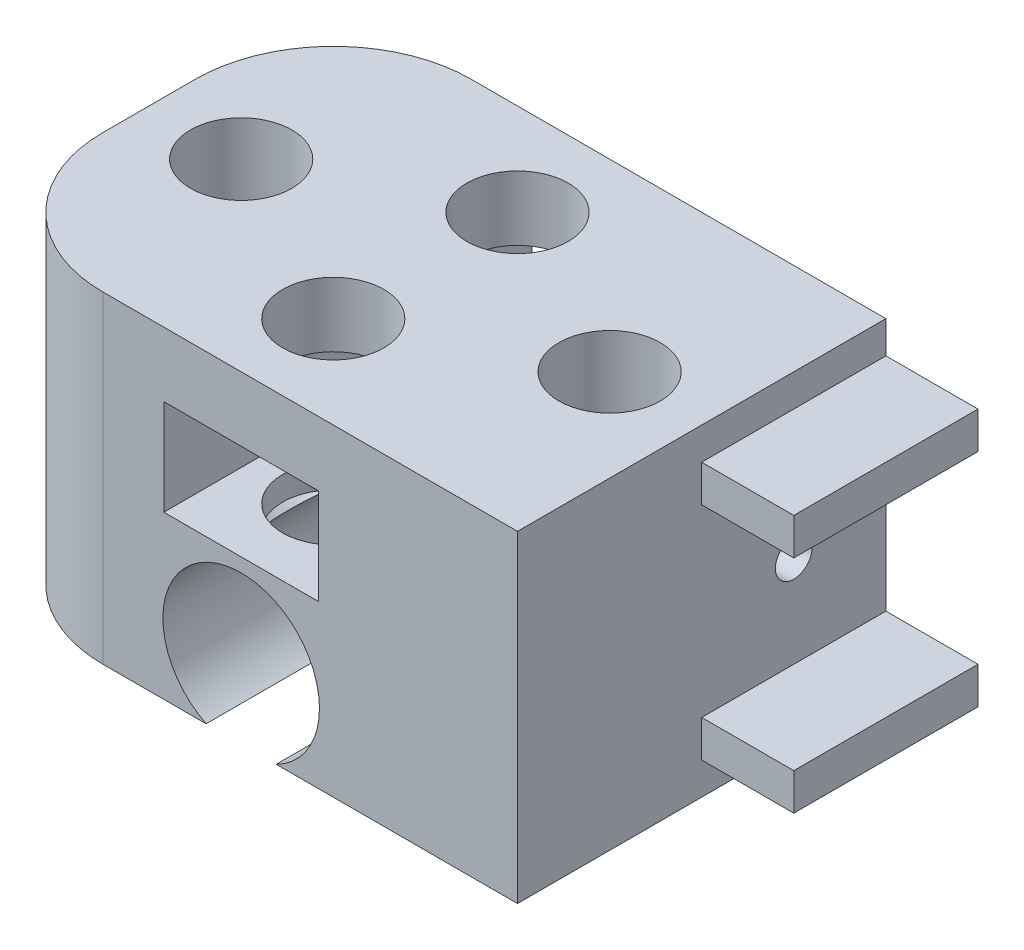
SolidWorks part; units mm, degrees
material "ABS PC"
ref_plane "Front Plane" through (0, 0, 0) normal (0, 0, 1) x (1, 0, 0)
ref_plane "Top Plane" through (0, 0, 0) normal (0, 1, 0) x (1, 0, 0)
ref_plane "Right Plane" through (0, 0, 0) normal (1, 0, 0) x (0, 0, -1)
sketch "Sketch1" plane through (0, 0, 0) normal (0, 0, 1) x (1, 0, 0)
  line L0 (0, 0) -> (30, 0)
  line L1 (0, 0) -> (0, 17.5)
  line L2 (30, 0) -> (30, 17.5)
  line L3 (0, 17.5) -> (30, 17.5)
  dimension "D1" = 30
  dimension "D2" = 17.5
extrude "Boss-Extrude1" add sketch "Sketch1" along normal blind 20
sketch "Sketch2" plane through (0, 0, 20) normal (0, 0, 1) x (1, 0, 0)
  line L0 (10.8, 8.8) -> (19.2, 8.8)
  line L1 (10.8, 8.8) -> (10.8, 14)
  line L2 (19.2, 8.8) -> (19.2, 14)
  line L3 (10.8, 14) -> (19.2, 14)
  line L5 (0, 17.5) -> (0, 0) construction
  line L6 (30, 17.5) -> (0, 17.5) construction
  circle A0 centre (15, 3.8) radius 4.25
  dimension "D1" = 8.5
  dimension "D7" = 15
  dimension "D2" = 8.4
  dimension "D3" = 5.2
  dimension "D4" = 4.2
  dimension "D5" = 5
  dimension "D6" = 3.5
extrude "Cut-Extrude1" cut sketch "Sketch2" against normal through all
hole_wizard "Ø5.5 (5.5) Diameter Hole1" positions "Sketch5" profile "Sketch4" hole size "Ø5.5" standard "Ansi Metric"
sketch "Sketch5" plane through (0, 17.5, 0) normal (0, 1, 0) x (-1, 0, 0)
  line L1 (-30, 20) -> (0, 20) construction
  line L2 (-30, 0) -> (0, 0) construction
  line L3 (0, 20) -> (0, 0) construction
  point P1 (-15, 15)
  point P12 (-15, 5)
  dimension "D1" = 5
  dimension "D2" = 5
  dimension "D3" = 15
sketch "Sketch4" plane through (15, 17.5, 15) normal (1, 0, 0) x (0, 0, 1)
  line L0 (0, 0) -> (0, 11.6524)
  line L1 (0, 11.6524) -> (2.75, 10)
  line L2 (2.75, 10) -> (2.75, 0)
  line L5 (2.75, 0) -> (0, 0)
  line L10 (0, 11.6524) -> (-2.75, 10) construction
  line L11 (0, -6.35) -> (0, 107.95) construction
  dimension "Hole Dia." = 5.5
  dimension "Hole Depth" = 10
  dimension "Drill Angle" = 118
hole_wizard "Ø5.5 (5.5) Diameter Hole2" positions "Sketch11" profile "Sketch10" hole size "Ø5.5" standard "Ansi Metric" end condition through all
sketch "Sketch11" plane through (0, 17.5, 0) normal (0, 1, 0) x (-1, 0, 0)
  line L0 (-30, 0) -> (0, 0) construction
  line L1 (-30, 20) -> (-30, 0) construction
  line L2 (0, 20) -> (0, 0) construction
  point P0 (-25, 10)
  point P1 (-5, 10)
  dimension "D1" = 10
  dimension "D2" = 5
  dimension "D3" = 5
sketch "Sketch10" plane through (25, 17.5, 10) normal (1, 0, 0) x (0, 0, 1)
  line L0 (0, 0) -> (0, 17.5)
  line L1 (0, 17.5) -> (2.75, 17.5)
  line L2 (2.75, 17.5) -> (2.75, 0)
  line L5 (2.75, 0) -> (0, 0)
  line L11 (0, -6.35) -> (0, 107.95) construction
  dimension "Thru Hole Dia." = 5.5
  dimension "Thru Hole Depth" = 17.5
fillet "Fillet5" radius 7.5 2 edges at (0, 8.75, 0) (0, 8.75, 20)
sketch "Sketch12" plane through (30, 0, 0) normal (1, 0, 0) x (0, 0, -1)
  line L0 (-20, 17.5) -> (0, 17.5) construction
  line L2 (0, 0) -> (0, 17.5) construction
  circle A0 centre (-5, 8.75) radius 1
  dimension "D1" = 2
  dimension "D2" = 8.75
  dimension "D3" = 5
extrude "Cut-Extrude2" cut sketch "Sketch12" against normal blind 8
sketch "Sketch13" plane through (30, 0, 0) normal (1, 0, 0) x (0, 0, -1)
  line L0 (0, 13.75) -> (-10, 13.75)
  line L1 (0, 13.75) -> (0, 15.75)
  line L2 (-10, 13.75) -> (-10, 15.75)
  line L3 (0, 15.75) -> (-10, 15.75)
  line L4 (0, 3.75) -> (-10, 3.75)
  line L5 (0, 3.75) -> (0, 1.75)
  line L6 (-10, 3.75) -> (-10, 1.75)
  line L7 (0, 1.75) -> (-10, 1.75)
  line L8 (0, 0) -> (0, 17.5) construction
  circle A0 centre (-5, 8.75) radius 1 construction
  dimension "D1" = 2
  dimension "D2" = 0
  dimension "D3" = 10
  dimension "D4" = 5
  dimension "D5" = 5
extrude "Boss-Extrude2" add sketch "Sketch13" along normal blind 5
